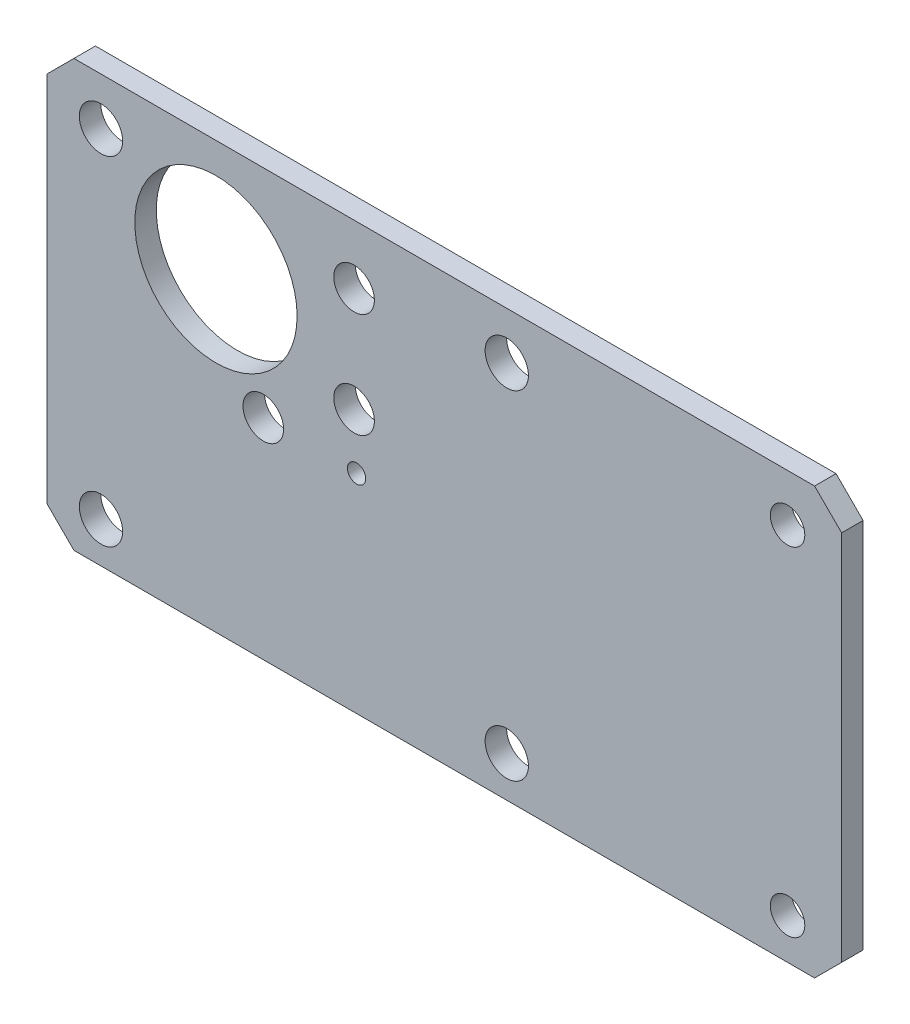
SolidWorks part; units mm, degrees
ref_plane "Front" through (0, 0, 0) normal (0, 0, 1) x (1, 0, 0)
ref_plane "Top" through (0, 0, 0) normal (0, 1, 0) x (1, 0, 0)
ref_plane "Right" through (0, 0, 0) normal (1, 0, 0) x (0, 0, -1)
ref_axis "side-side" through (80.9, 0, 0) along (-1, 0, 0)
ref_axis "up-down" through (0, 50, 0) along (0, -1, 0)
ref_axis "front-back" through (0, 0, -80.9) along (0, 0, 1)
sketch "Sketch1" plane through (0, 0, 0) normal (0, 0, 1) x (1, 0, 0)
  line L0 (85.516, -393.7) -> (85.516, 16.5) construction
  line L1 (-32, 12.5) -> (-32, -42.5) construction
  line L2 (-28, -46.5) -> (40, -46.5) construction
  line L3 (40, 16.5) -> (-28, 16.5) construction
  line L4 (85.516, -46.5) -> (85.516, 16.5)
  line L5 (-32, 16.5) -> (-32, -46.5)
  line L6 (-32, -46.5) -> (85.516, -46.5)
  line L7 (85.516, 16.5) -> (-32, 16.5)
  circle A0 centre (-24, 9.5) radius 3.2004
  circle A1 centre (13.4234, 7.75) radius 3
  circle A2 centre (-7, 0) radius 12
  circle A3 centre (-7, 0) radius 12
  circle A4 centre (13.4234, -7.75) radius 3
  circle A5 centre (36, 9.5) radius 2.9337 construction
  circle A6 centre (-24, -40.5) radius 3.2004
  circle A7 centre (0, -15.5) radius 3
  circle A8 centre (36, -40.5) radius 3.2004
  circle A9 centre (36, 9.5) radius 3.2004
  circle A10 centre (77.516, 9.5) radius 3.2004 construction
  circle A11 centre (77.516, -40.5) radius 3.2004 construction
  point P10 (-24, -40.5)
  point P12 (36, 9.5)
  point P16 (-24, 9.5)
  point P23 (36, -40.5)
  point P29 (77.516, 9.5)
  point P30 (77.516, -40.5)
  dimension "D2" = 6
  dimension "D4" = 6.4008
  dimension "D3" = 8
  dimension "D1" = 1
extrude "Boss-Extrude1" add sketch "Sketch1" against normal blind 3.175
chamfer "Chamfer1" distance 4 angle 45 4 edges at (85.516, -46.5, -1.5875) (85.516, 16.5, -1.5875) (-32, -46.5, -1.5875) (-32, 16.5, -1.5875)
hole_wizard "1/4-20 Tapped Hole1" positions "Sketch2" profile "Sketch3" tap size "1/4-20" standard "ANSI Inch" end condition through all
sketch "Sketch2" plane through (0, 0, 0) normal (0, 0, 1) x (1, 0, 0)
  point P0 (77.516, 9.5)
  point P3 (77.516, -40.5)
sketch "Sketch3" plane through (77.516, 9.5, 0) normal (1, 0, 0) x (0, -1, 0)
  line L0 (0, 0) -> (0, 3.175)
  line L1 (0, 3.175) -> (2.5527, 3.175)
  line L2 (2.5527, 3.175) -> (2.5527, 0)
  line L5 (2.5527, 0) -> (0, 0)
  line L11 (0, -6.35) -> (0, 107.95) construction
  dimension "Thread Major Dia." = 5.1054
  dimension "Thru Tap Drill Depth" = 3.175
hole_wizard "#6-32 Tapped Hole1" positions "Sketch4" profile "Sketch5" tap size "#6-32" standard "ANSI Inch" end condition through all
sketch "Sketch4" plane through (0, 0, 0) normal (0, 0, 1) x (1, 0, 0)
  point P0 (13.7909, -15.7518)
sketch "Sketch5" plane through (13.7909, -15.7518, 0) normal (1, 0, 0) x (0, -1, 0)
  line L0 (0, 0) -> (0, 3.175)
  line L1 (0, 3.175) -> (1.3525, 3.175)
  line L2 (1.3525, 3.175) -> (1.3525, 0)
  line L5 (1.3525, 0) -> (0, 0)
  line L11 (0, -6.35) -> (0, 107.95) construction
  dimension "Thread Major Dia." = 2.7051
  dimension "Thru Tap Drill Depth" = 3.175
